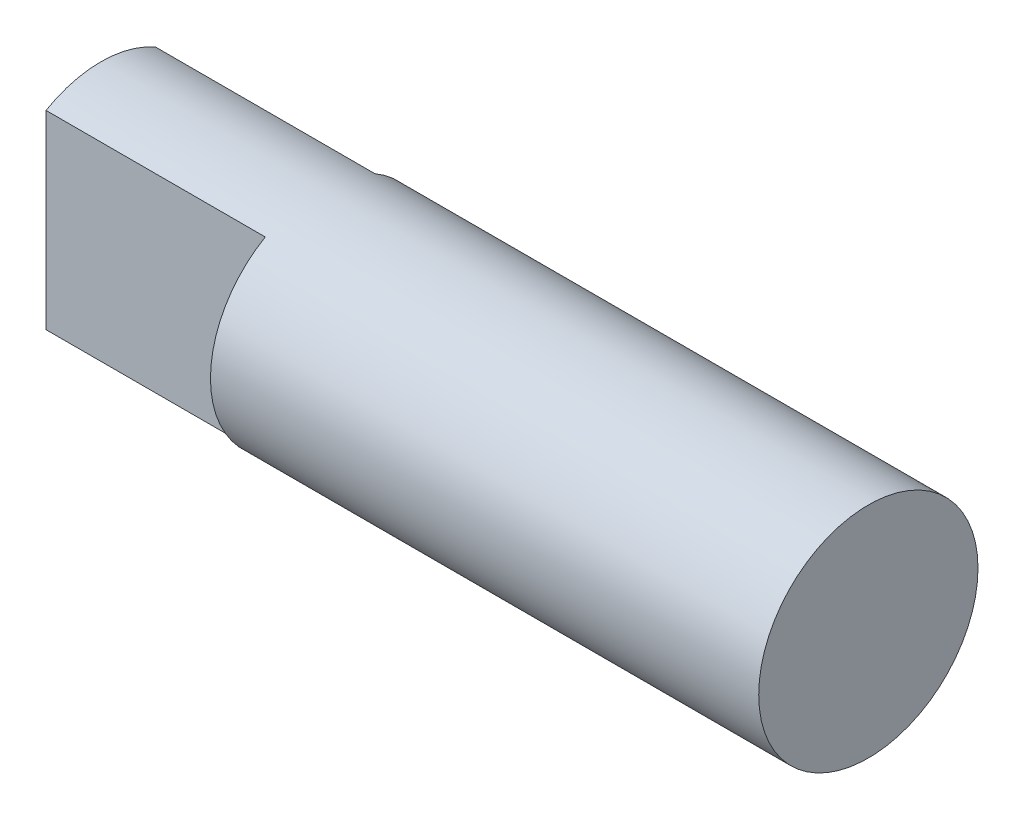
SolidWorks part; units mm, degrees
ref_plane "Front Plane" through (0, 0, 0) normal (0, 0, 1) x (1, 0, 0)
ref_plane "Top Plane" through (0, 0, 0) normal (0, 1, 0) x (1, 0, 0)
ref_plane "Right Plane" through (0, 0, 0) normal (1, 0, 0) x (0, 0, -1)
sketch "Sketch1" plane through (0, 0, 0) normal (1, 0, 0) x (0, 0, -1)
  circle A0 centre (0, 0) radius 12.7
  dimension "D1" = 25.4
extrude "Boss-Extrude1" add sketch "Sketch1" along normal blind 76.2 and the other way blind 12.7
sketch "Sketch2" plane through (0, 0, 0) normal (0, 1, 0) x (1, 0, 0)
  line L1 (-12.7, -12.7) -> (12.7, -12.7)
  line L2 (-12.7, -12.7) -> (-12.7, -6.35)
  line L3 (-12.7, -6.35) -> (12.7, -6.35)
  line L4 (12.7, -12.7) -> (12.7, -6.35)
  line L5 (-12.7, 12.7) -> (12.7, 12.7)
  line L6 (-12.7, 12.7) -> (-12.7, 6.35)
  line L7 (-12.7, 6.35) -> (12.7, 6.35)
  line L8 (12.7, 12.7) -> (12.7, 6.35)
  dimension "D1" = 25.4
  dimension "D2" = 6.35
extrude "Cut-Extrude1" cut sketch "Sketch2" against normal through all both and the other way through all
